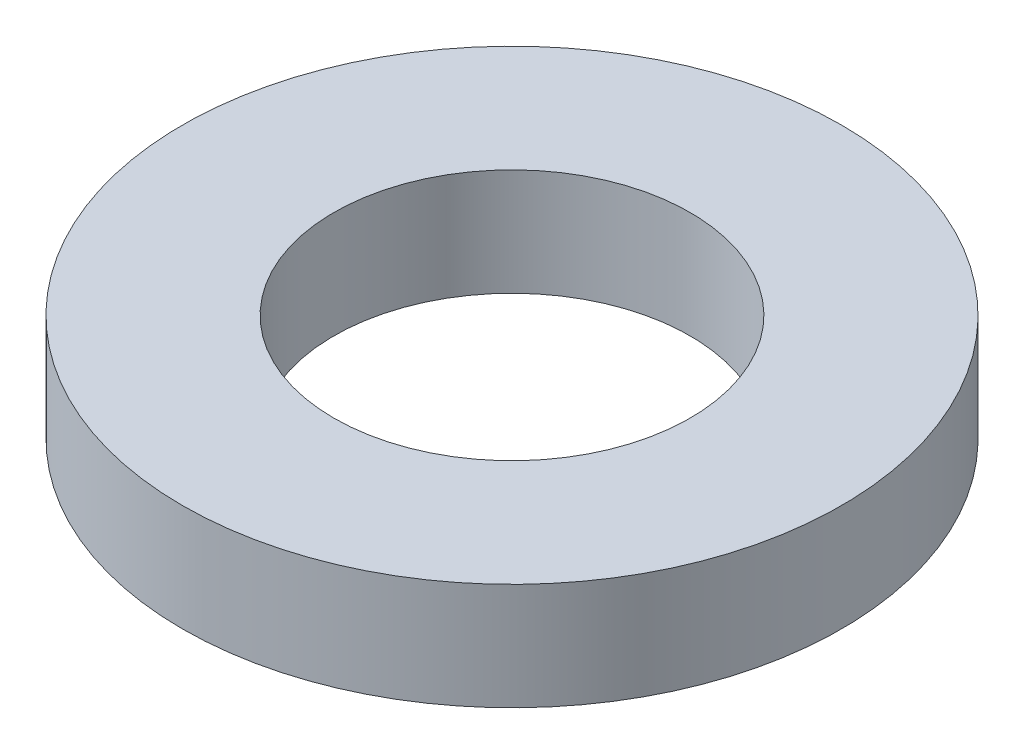
SolidWorks part; units mm, degrees
ref_plane "Front Plane" through (0, 0, 0) normal (0, 0, 1) x (1, 0, 0)
ref_plane "Top Plane" through (0, 0, 0) normal (0, 1, 0) x (1, 0, 0)
ref_plane "Right Plane" through (0, 0, 0) normal (1, 0, 0) x (0, 0, -1)
sketch "Sketch1" plane through (0, 0, 0) normal (0, 1, 0) x (1, 0, 0)
  circle A0 centre (0, 0) radius 92.5
  dimension "FLANGE_OD" = 185
extrude "Boss-Extrude1" add sketch "Sketch1" along normal blind 30
sketch "Sketch2" plane through (0, 0, 0) normal (0, 1, 0) x (1, 0, 0)
  circle A0 centre (0, 0) radius 50
  dimension "BORE_D" = 100
extrude "Cut-Extrude1" cut sketch "Sketch2" along normal through all
sketch "Sketch3" plane through (0, 30, 0) normal (0, 1, 0) x (1, 0, 0)
  circle A0 centre (0, 0) radius 36.5087 construction
  circle A1 centre (-36.5087, 0) radius 6.6127
  dimension "BOLT_D" = 13.2255
  dimension "BOLT_PCD" = 73.0174
extrude "Cut-Extrude2" cut sketch "Sketch3" against normal blind 28.212 rebuild error yes
pattern_circular "CirPattern1" count 3 over 360 rebuild error yes
